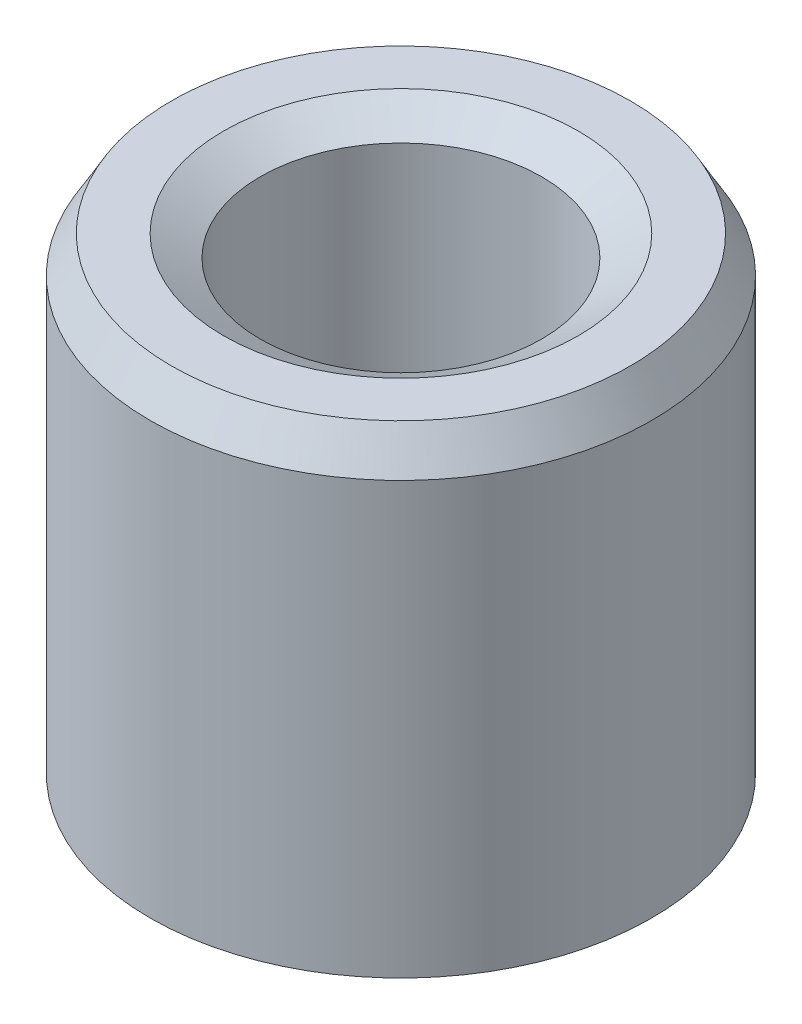
SolidWorks part; units mm, degrees
ref_plane "Front Plane" through (0, 0, 0) normal (0, 0, 1) x (1, 0, 0)
ref_plane "Top Plane" through (0, 0, 0) normal (0, 1, 0) x (1, 0, 0)
ref_plane "Right Plane" through (0, 0, 0) normal (1, 0, 0) x (0, 0, -1)
sketch "Sketch1" plane through (0, 0, 0) normal (0, 1, 0) x (1, 0, 0)
  circle A0 centre (0, 0) radius 5
  dimension "SLEEVE_OD" = 10
extrude "Boss-Extrude1" add sketch "Sketch1" along normal blind 9.7468
sketch "Sketch2" plane through (0, 0, 0) normal (0, 1, 0) x (1, 0, 0)
  circle A0 centre (0, 0) radius 2.8057
  dimension "BORE_D" = 5.6114
extrude "Cut-Extrude1" cut sketch "Sketch2" along normal through all
chamfer "Chamfer1" distance 0.7311 angle 30.056 4 edges at (0, 9.7468, 2.8057) (0, 0, 2.8057) (0, 0, 5) (0, 9.7468, 5) first distance on face at (0, 9.7468, 2.8057) first distance on face at (0, 0, 2.8057) first distance on face at (0, 9.7468, 5)
